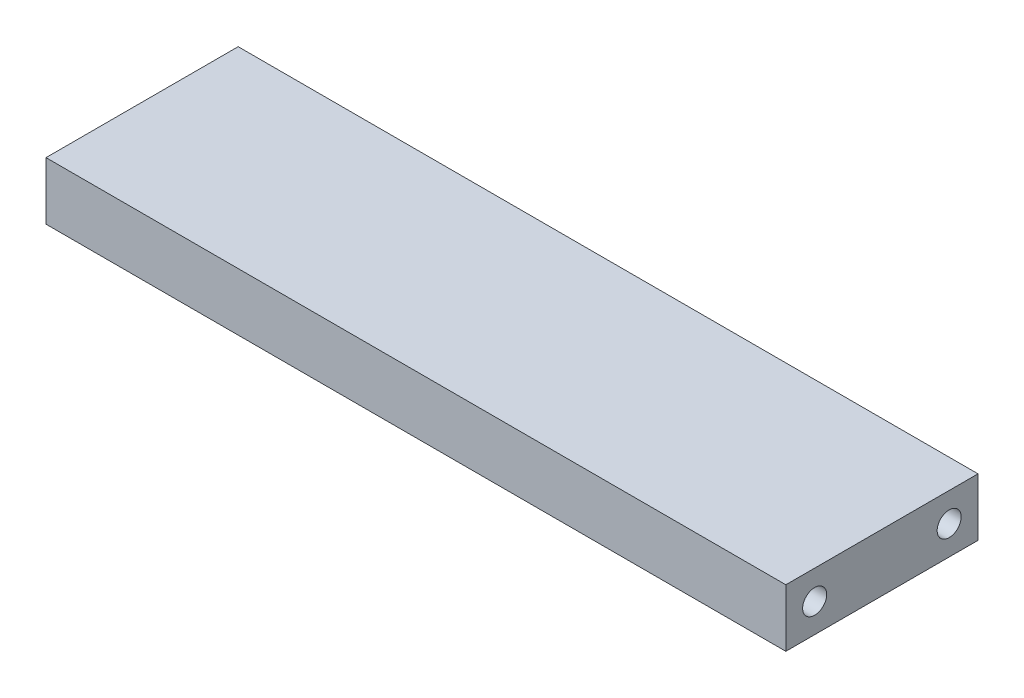
SolidWorks part; units mm, degrees
material "1060 Alloy"
ref_plane "Front Plane" through (0, 0, 0) normal (0, 0, 1) x (1, 0, 0)
ref_plane "Top Plane" through (0, 0, 0) normal (0, 1, 0) x (1, 0, 0)
ref_plane "Right Plane" through (0, 0, 0) normal (1, 0, 0) x (0, 0, -1)
sketch "Sketch1" plane through (0, 0, 0) normal (0, 1, 0) x (1, 0, 0)
  line L1 (0, 0) -> (77, 0)
  line L2 (0, 0) -> (0, 20)
  line L3 (0, 20) -> (77, 20)
  line L4 (77, 0) -> (77, 20)
  dimension "D1" = 20
  dimension "D2" = 77
extrude "Boss-Extrude1" add sketch "Sketch1" along normal blind 6
hole_wizard "Tap Drill for M3 Tap1" positions "Sketch4" profile "Sketch3" hole size "M3" standard "ISO"
sketch "Sketch4" plane through (0, 0, 0) normal (-1, 0, 0) x (0, 0, 1)
  line L0 (-20, 0) -> (0, 0) construction
  line L1 (-20, 6) -> (-20, 0) construction
  line L2 (0, 6) -> (0, 0) construction
  point P0 (-17, 3)
  point P2 (-3, 3)
  dimension "D1" = 3
  dimension "D2" = 3
  dimension "D3" = 3
sketch "Sketch3" plane through (0, 3, -17) normal (0, 1, 0) x (0, 0, 1)
  line L0 (0, 0) -> (0, 10.7511)
  line L1 (0, 10.7511) -> (1.25, 10)
  line L2 (1.25, 10) -> (1.25, 0)
  line L5 (1.25, 0) -> (0, 0)
  line L10 (0, 10.7511) -> (-1.25, 10) construction
  line L11 (0, -6.35) -> (0, 107.95) construction
  dimension "Hole Dia." = 2.5
  dimension "Hole Depth" = 10
  dimension "Drill Angle" = 118
hole_wizard "Tap Drill for M3 Tap2" positions "Sketch6" profile "Sketch5" hole size "M3" standard "ISO"
sketch "Sketch6" plane through (77, 0, 0) normal (1, 0, 0) x (0, 0, -1)
  line L0 (0, 0) -> (20, 0) construction
  line L1 (0, 6) -> (0, 0) construction
  line L2 (20, 6) -> (20, 0) construction
  point P0 (3, 3)
  point P2 (17, 3)
  dimension "D1" = 3
  dimension "D2" = 3
  dimension "D3" = 3
sketch "Sketch5" plane through (77, 3, -3) normal (0, 1, 0) x (0, 0, -1)
  line L0 (0, 0) -> (0, 10.7511)
  line L1 (0, 10.7511) -> (1.25, 10)
  line L2 (1.25, 10) -> (1.25, 0)
  line L5 (1.25, 0) -> (0, 0)
  line L10 (0, 10.7511) -> (-1.25, 10) construction
  line L11 (0, -6.35) -> (0, 107.95) construction
  dimension "Hole Dia." = 2.5
  dimension "Hole Depth" = 10
  dimension "Drill Angle" = 118
